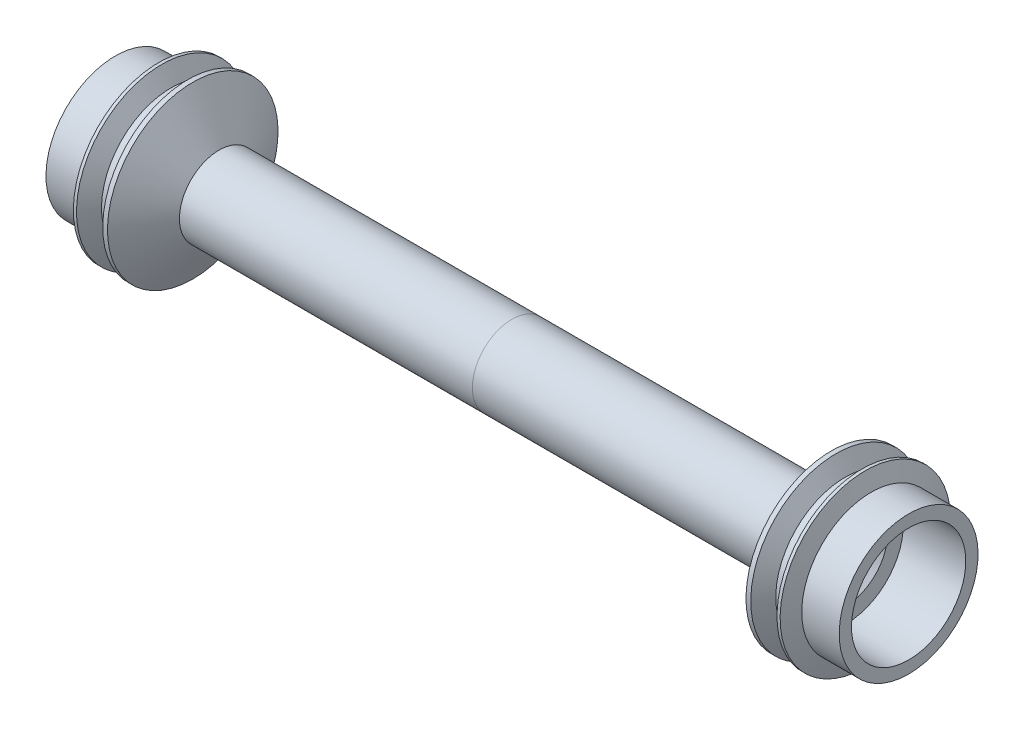
SolidWorks part; units mm, degrees
ref_plane "Front Plane" through (0, 0, 0) normal (0, 0, 1) x (1, 0, 0)
ref_plane "Top Plane" through (0, 0, 0) normal (0, 1, 0) x (1, 0, 0)
ref_plane "Right Plane" through (0, 0, 0) normal (1, 0, 0) x (0, 0, -1)
sketch "Sketch2" plane through (0, 0, 0) normal (0, 0, 1) x (1, 0, 0)
  line L0 (0, 0) -> (0, 28.4375) construction
  line L1 (-31.75, 4.575) -> (-26.75, 4.575) construction
  line L2 (-31.75, 4.575) -> (-31.75, -4.575) construction
  line L3 (-31.75, -4.575) -> (-26.75, -4.575) construction
  line L4 (-26.75, 4.575) -> (-26.75, -4.575) construction
  line L5 (-31.75, 4.575) -> (-26.75, -4.575) construction
  line L6 (-31.75, -4.575) -> (-26.75, 4.575) construction
  line L7 (26.75, 4.5) -> (36.8332, 4.5) construction
  line L8 (26.75, 4.5) -> (26.75, -4.5) construction
  line L9 (26.75, -4.5) -> (36.8332, -4.5) construction
  line L10 (36.8332, 4.5) -> (36.8332, -4.5) construction
  line L11 (26.75, 4.5) -> (36.8332, -4.5) construction
  line L12 (26.75, -4.5) -> (36.8332, 4.5) construction
  line L13 (-31.75, 0) -> (36.8332, 0) construction
  line L14 (-31.75, 5.5562) -> (-28.75, 5.5562)
  line L15 (-28.75, 5.5562) -> (-28.2878, 6.8262)
  line L16 (-28.2878, 6.8262) -> (-28.0382, 6.8262)
  line L19 (-25.9368, 6.8262) -> (-25.5558, 6.8262)
  line L20 (-25.5558, 6.8262) -> (-23.4477, 3.175)
  line L21 (-23.4477, 3.175) -> (0, 3.175)
  line L22 (-31.75, 5.5562) -> (-31.75, 4.575)
  line L23 (-31.75, 4.575) -> (-26.75, 4.575)
  line L24 (-26.75, 4.575) -> (-26.75, 0)
  line L25 (-26.75, 0) -> (0, 0)
  line L26 (0, 0) -> (0, 3.175)
  line L27 (-33.5594, -5.5562) -> (-33.5594, 5.5562) construction
  line L28 (-26.9875, 5.5562) -> (-26.9875, 7.68) construction
  line L29 (-26.9875, 5.5562) -> (26.9875, 5.5562) construction
  line L30 (-31.75, 5.5562) -> (31.75, 5.5562) construction
  line L31 (0, 1.6) -> (-12.5, 1.6)
  line L32 (-12.5, 1.6) -> (-14.1, 0)
  line L33 (-12.5, 1.6) -> (-12.5, -1.6) construction
  line L34 (-12.5, 1.6) -> (12.5, 1.6) construction
  line L35 (-26.75, 1.7145) -> (-21.925, 1.7145)
  line L36 (-21.925, 1.7145) -> (-21.925, 0)
  line L37 (-26.75, 3.305) -> (-26.242, 2.797)
  line L38 (-21.925, 1.7145) -> (-34.925, 1.7145) construction
  line L39 (-21.925, 1.7145) -> (-21.925, -1.7145) construction
  line L40 (-21.925, -1.7145) -> (-34.925, -1.7145) construction
  line L41 (-34.925, 1.7145) -> (-34.925, -1.7145) construction
  line L42 (-26.242, 2.797) -> (-26.242, 0)
  line L43 (-27.305, 5.5562) -> (-26.67, 5.5562)
  line L44 (-28.0382, 6.8262) -> (-27.305, 5.5562)
  line L45 (-25.9368, 6.8262) -> (-26.67, 5.5562)
  point P0 (-29.25, 0)
  point P5 (31.7916, 0)
  point P27 (-33.5594, 0)
  point P29 (-12.5, 0)
  point P33 (0, 5.5562)
  point P36 (0, 1.6)
  point P48 (-21.925, 0)
  point P51 (0, 5.5562)
  point P53 (-26.9875, 5.5562)
  dimension "D1" = 5
  dimension "D3" = 3.175
  dimension "D4" = 11.1125
  dimension "D5" = 9.15
  dimension "D6" = 60
  dimension "D7" = 60
  dimension "D8" = 1.27
  dimension "D9" = 70
  dimension "D10" = 53.975
  dimension "D11" = 63.5
  dimension "D12" = 0.381
  dimension "D13" = 45
  dimension "D14" = 25
  dimension "D15" = 3.2
  dimension "D16" = 3.429
  dimension "D17" = 3.175
  dimension "D18" = 1.27
  dimension "D19" = 0.508
  dimension "D20" = 45
  dimension "D21" = 13
  dimension "D22" = 3
  dimension "D23" = 0.635
revolve "Revolve1" add sketch "Sketch2" angle 360 about L13 region at (-16.734, 2.5743, 0)
mirror "Mirror1" about plane through (0, 0, 0) normal (1, 0, 0) of bodies 101
chamfer "Chamfer1" distance 0.508 angle 45 1 edges at (-31.75, -4.575, 0)
